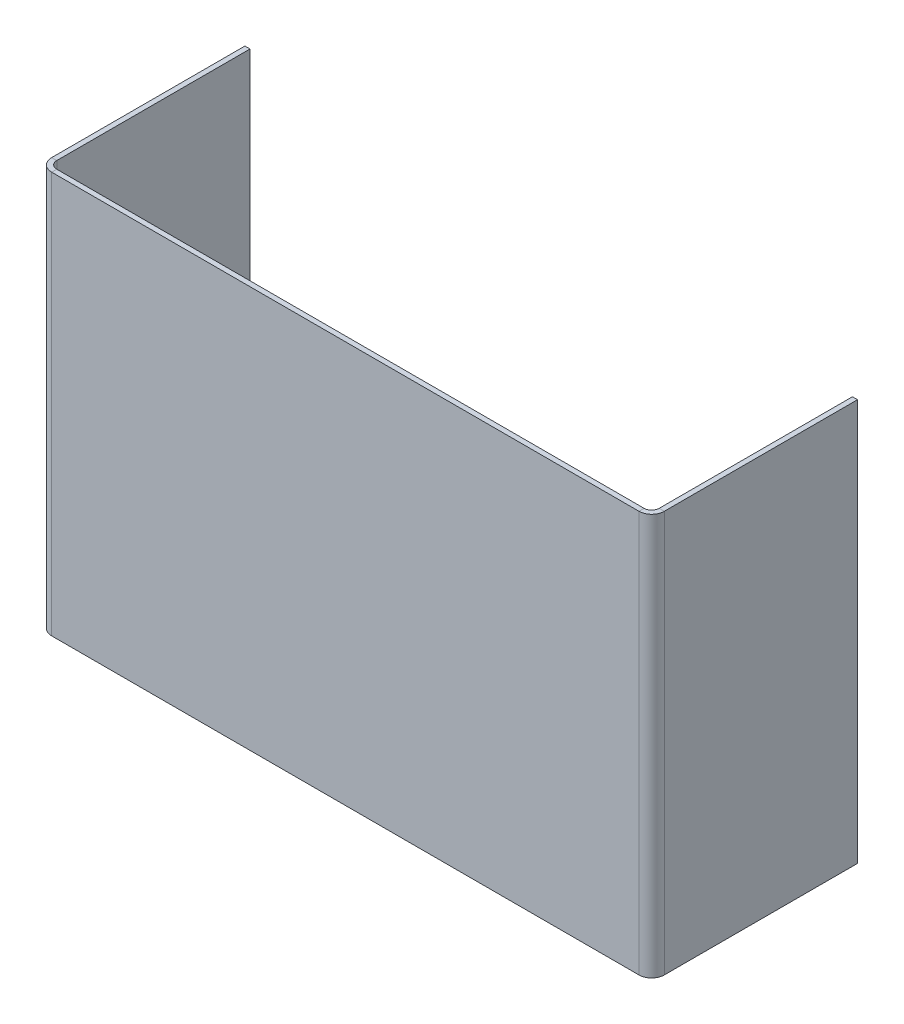
SolidWorks part; units mm, degrees
note: The reader was unsure of these and kept them because the rebuilt part matched: flange length of "Edge-Flange1".
ref_plane "Front Plane" through (0, 0, 0) normal (0, 0, 1) x (1, 0, 0)
ref_plane "Top Plane" through (0, 0, 0) normal (0, 1, 0) x (1, 0, 0)
ref_plane "Right Plane" through (0, 0, 0) normal (1, 0, 0) x (0, 0, -1)
sketch "Sketch1" plane through (0, 0, 0) normal (0, 0, 1) x (1, 0, 0)
  line L1 (-76.2, -50.8) -> (76.2, -50.8)
  line L2 (-76.2, -50.8) -> (-76.2, 50.8)
  line L3 (-76.2, 50.8) -> (76.2, 50.8)
  line L4 (76.2, -50.8) -> (76.2, 50.8)
  line L5 (-76.2, -50.8) -> (76.2, 50.8) construction
  line L6 (-76.2, 50.8) -> (76.2, -50.8) construction
  point P0 (0, 0)
  dimension "D1" = 152.4
  dimension "D2" = 101.6
base flange "Base-Flange1" sketch "Sketch1" thickness 1.2903 reverse thickness direction no parameters "D1"=1.905
edge flange "Edge-Flange1" sketch "Sketch10" flange profiles "Sketch10", "Sketch11" flange angle 90 flange length 50.8 flange position material outside bend radius 1.905 thickness 1.2903 relief rectangular parameters "D6"=10, "D8"=0.254
sketch "Sketch10" plane through (-76.2, 0, -1.2903) normal (1, 0, 0) x (0, -1, 0)
  line L1 (50.8, 0) -> (-50.8, 0) construction
  line L2 (-50.8, 0) -> (-50.8, 50.8)
  line L3 (-50.8, 50.8) -> (50.8, 50.8)
  line L4 (50.8, 50.8) -> (50.8, 0)
  line L5 (50.8, 0) -> (-50.8, 0)
sketch "Sketch11" plane through (76.2, 0, -1.2903) normal (-1, 0, 0) x (0, 1, 0)
  line L1 (50.8, 0) -> (-50.8, 0) construction
  line L2 (-50.8, 0) -> (-50.8, 50.8)
  line L3 (-50.8, 50.8) -> (50.8, 50.8)
  line L4 (50.8, 50.8) -> (50.8, 0)
  line L5 (50.8, 0) -> (-50.8, 0)
bend "EdgeBend1" bend radius 1.905 bend angle 90 parameters "D5"=1
bend "EdgeBend2" bend radius 1.905 bend angle 90 parameters "D5"=2
sketch "Bend-Lines1" [suppressed] plane through (0, 0, 0) normal (0, 1, 0) x (1, 0, 0)
sketch "Bounding-Box1" [suppressed] plane through (0, 0, 0) normal (0, 1, 0) x (1, 0, 0)
sheet metal parameters "Sheet-Metal(1)" thickness 1.2903 parameters "D1"=1.905
flat pattern "Flat-Pattern(1)" [suppressed]
sketch "Bend-Lines2" plane through (0, 0, 0) normal (0, 1, 0) x (1, 0, 0)
sketch "Bounding-Box2" [suppressed] plane through (0, 0, 0) normal (0, 1, 0) x (1, 0, 0)
sheet metal parameters "Sheet-Metal(2)" thickness 1.2903 parameters "D1"=1.905
flat pattern "Flat-Pattern(1)"
sketch "Bend-Lines2" plane through (0, 0, 0) normal (0, 0, 1) x (1, 0, 0)
  line L0 (76.2979, -50.8) -> (76.2979, 50.8) construction
  line L1 (-76.2979, 50.8) -> (-76.2979, -50.8) construction
  line L2 (76.2979, -50.8) -> (76.2979, 50.8) construction
  line L3 (-76.2979, 50.8) -> (-76.2979, -50.8) construction
sketch3d "Bounding-Box2" [suppressed]
  line L0 (-127.1958, -50.8, 0) -> (127.1958, -50.8, 0) construction
  line L1 (-127.1958, 50.8, 0) -> (127.1958, 50.8, 0) construction
  line L2 (-127.1958, -50.8, 0) -> (-127.1958, 50.8, 0) construction
  line L3 (127.1958, -50.8, 0) -> (127.1958, 50.8, 0) construction
bend of the flat pattern "Flatten-<EdgeBend1>1"
bend of the flat pattern "Flatten-<EdgeBend2>1"
